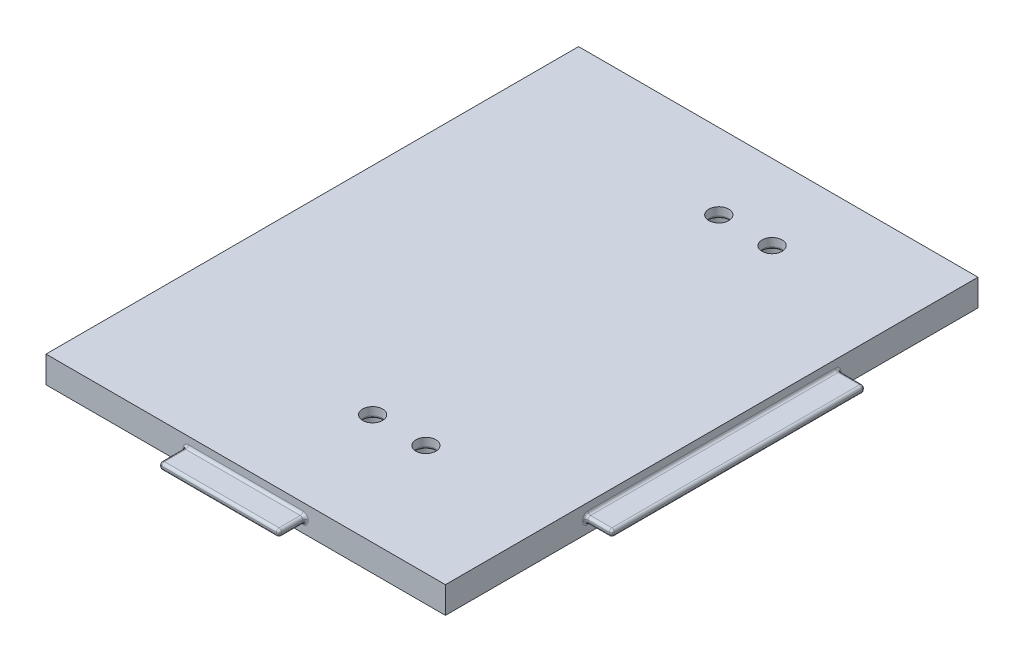
SolidWorks part; units mm, degrees
ref_plane "Front Plane" through (0, 0, 0) normal (0, 0, 1) x (1, 0, 0)
ref_plane "Top Plane" through (0, 0, 0) normal (0, 1, 0) x (1, 0, 0)
ref_plane "Right Plane" through (0, 0, 0) normal (1, 0, 0) x (0, 0, -1)
sketch "Sketch1" plane through (0, 0, 0) normal (0, 1, 0) x (1, 0, 0)
  line L1 (75, 100) -> (-75, 100)
  line L2 (75, 100) -> (75, -100)
  line L3 (75, -100) -> (-75, -100)
  line L4 (-75, 100) -> (-75, -100)
  line L5 (75, 100) -> (-75, -100) construction
  line L6 (75, -100) -> (-75, 100) construction
  point P0 (0, 0)
  dimension "D1" = 150
  dimension "D2" = 200
extrude "Boss-Extrude1" add sketch "Sketch1" along normal blind 10
sketch "Sketch2" plane through (-75, 0, 0) normal (-1, 0, 0) x (0, 0, 1)
  line L0 (-100, 10) -> (100, 10) construction
  line L1 (50, 6.5) -> (-50, 6.5)
  line L2 (50, 6.5) -> (50, 3.5)
  line L3 (50, 3.5) -> (-50, 3.5)
  line L4 (-50, 6.5) -> (-50, 3.5)
  line L5 (50, 6.5) -> (-50, 3.5) construction
  line L6 (50, 3.5) -> (-50, 6.5) construction
  point P0 (0, 5)
  point P5 (0, 0)
  point P8 (0, 0)
  dimension "D1" = 100
  dimension "D2" = 5
  dimension "D3" = 3
extrude "Cut-Extrude1" cut sketch "Sketch2" against normal blind 10
chamfer "Chamfer1" distance 10 angle 45 2 edges at (-75, 5, 50) (-75, 5, -50)
sketch "Sketch3" plane through (0, 0, -100) normal (0, 0, -1) x (-1, 0, 0)
  line L0 (-75, 10) -> (75, 10) construction
  line L1 (25, 6.5) -> (-25, 6.5)
  line L2 (25, 6.5) -> (25, 3.5)
  line L3 (25, 3.5) -> (-25, 3.5)
  line L4 (-25, 6.5) -> (-25, 3.5)
  line L5 (25, 6.5) -> (-25, 3.5) construction
  line L6 (25, 3.5) -> (-25, 6.5) construction
  point P0 (0, 5)
  point P5 (0, 0)
  dimension "D1" = 50
  dimension "D2" = 5
  dimension "D3" = 3
extrude "Cut-Extrude2" cut sketch "Sketch3" against normal blind 10
chamfer "Chamfer2" distance 10 angle 45 2 edges at (-25, 5, -100) (25, 5, -100)
fillet "Fillet1" radius 1 12 edges at (30, 3.5, -95) (30, 6.5, -95) (-30, 3.5, -95) (-30, 6.5, -95) (0, 3.5, -90) (0, 6.5, -90) (-70, 6.5, 55) (-65, 6.5, 0) (-70, 6.5, -55) (-70, 3.5, -55) (-65, 3.5, 0) (-70, 3.5, 55)
sketch "Sketch4" plane through (0, 0, 100) normal (0, 0, 1) x (1, 0, 0)
  line L0 (-75, 10) -> (75, 10) construction
  line L1 (22.5, 6.25) -> (-22.5, 6.25)
  line L2 (22.5, 6.25) -> (22.5, 3.75)
  line L3 (22.5, 3.75) -> (-22.5, 3.75)
  line L4 (-22.5, 6.25) -> (-22.5, 3.75)
  line L5 (22.5, 6.25) -> (-22.5, 3.75) construction
  line L6 (22.5, 3.75) -> (-22.5, 6.25) construction
  point P0 (0, 5)
  point P8 (0, 0)
  dimension "D1" = 2.5
  dimension "D2" = 5
  dimension "D3" = 45
extrude "Boss-Extrude2" add sketch "Sketch4" along normal blind 10
sketch "Sketch5" plane through (75, 0, 0) normal (1, 0, 0) x (0, 0, -1)
  line L0 (-100, 10) -> (-100, 0) construction
  line L1 (47.5, 6.25) -> (-47.5, 6.25)
  line L2 (47.5, 6.25) -> (47.5, 3.75)
  line L3 (47.5, 3.75) -> (-47.5, 3.75)
  line L4 (-47.5, 6.25) -> (-47.5, 3.75)
  line L5 (47.5, 6.25) -> (-47.5, 3.75) construction
  line L6 (47.5, 3.75) -> (-47.5, 6.25) construction
  line L8 (-100, 10) -> (100, 10) construction
  point P0 (0, 5)
  point P5 (0, 0)
  point P6 (0, 0)
  point P11 (2.4919, 10)
  dimension "D1" = 95
  dimension "D2" = 2.5
  dimension "D3" = 100
  dimension "D4" = 5
extrude "Boss-Extrude3" add sketch "Sketch5" along normal blind 10
fillet "Fillet2" radius 1 24 edges at (0, 6.25, 100) (0, 3.75, 100) (75, 6.25, 0) (75, 3.75, 0) (22.5, 3.75, 105) (22.5, 6.25, 105) (22.5, 5, 100) (-22.5, 6.25, 105) (-22.5, 3.75, 105) (-22.5, 5, 100) (0, 6.25, 110) (22.5, 5, 110) (0, 3.75, 110) (-22.5, 5, 110) (80, 3.75, -47.5) (80, 6.25, -47.5) (75, 5, -47.5) (80, 6.25, 47.5) (80, 3.75, 47.5) (75, 5, 47.5) (85, 6.25, 0) (85, 5, -47.5) (85, 3.75, 0) (85, 5, 47.5)
sketch "Sketch6" plane through (0, 10, 0) normal (0, 1, 0) x (1, 0, 0)
  line L0 (-75, -100) -> (75, -100) construction
  line L1 (75, -100) -> (75, 100) construction
  line L2 (-75, 100) -> (-75, -100) construction
  circle A0 centre (26.062, 71.599) radius 3.75
  circle A1 centre (26.062, -58.401) radius 3.75
  circle A2 centre (6.06, 71.599) radius 3.75
  circle A3 centre (6.06, -58.401) radius 3.75
  point P12 (0, 0)
  point P14 (-110.6794, -88.6113)
  point P16 (0, 0)
  dimension "D2" = 7.5
  dimension "D3" = 7.5
  dimension "D6" = 7.5
  dimension "D7" = 7.5
  dimension "D1" = 130
  dimension "D4" = 41.599
  dimension "D5" = 48.938
  dimension "D8" = 130
  dimension "D9" = 81.06
extrude "Cut-Extrude3" cut sketch "Sketch6" against normal blind 10
sketch "Sketch7" plane through (0, 0, 0) normal (0, -1, 0) x (1, 0, 0)
  circle A0 centre (6.06, -71.599) radius 5
  circle A1 centre (26.062, -71.599) radius 5
  circle A2 centre (26.062, 58.401) radius 5
  circle A3 centre (6.06, 58.401) radius 5
  dimension "D1" = 10
  dimension "D2" = 10
  dimension "D3" = 10
  dimension "D4" = 10
extrude "Cut-Extrude4" cut sketch "Sketch7" against normal blind 6
fillet "Fillet3" radius 1 8 edges at (26.062, 6, -75.349) (6.06, 6, -75.349) (6.06, 6, 54.651) (26.062, 6, 54.651) (26.062, 0, 53.401) (6.06, 0, 53.401) (26.062, 0, -76.599) (6.06, 0, -76.599)
